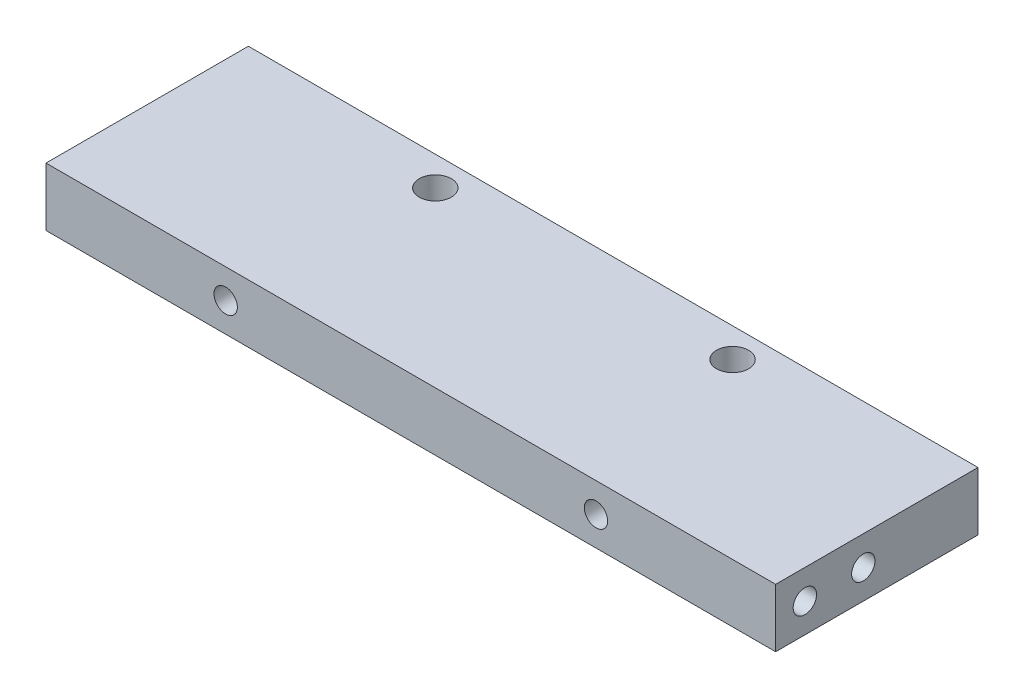
SolidWorks part; units mm, degrees
material "6061-T6 (SS)"
ref_plane "前视基准面" through (0, 0, 0) normal (0, 0, 1) x (1, 0, 0)
ref_plane "上视基准面" through (0, 0, 0) normal (0, 1, 0) x (1, 0, 0)
ref_plane "右视基准面" through (0, 0, 0) normal (1, 0, 0) x (0, 0, -1)
other "Configuration Table"
sketch "草图1" plane through (0, 0, 0) normal (0, 0, 1) x (1, 0, 0)
  line L1 (-0.3, -4.3) -> (49.65, -4.3)
  line L2 (-0.3, -4.3) -> (-0.3, -0.3)
  line L3 (-0.3, -0.3) -> (49.65, -0.3)
  line L4 (49.65, -4.3) -> (49.65, -0.3)
  dimension "D1" = 49.65
  dimension "D2" = 0.3
  dimension "D3" = 0.3
  dimension "D4" = 4.3
extrude "Main_Stock" add sketch "草图1" along normal blind 8.8519 from offset 2.2481
sketch "草图2" plane through (0, 0, 11.1) normal (0, 0, 1) x (1, 0, 0)
  circle A0 centre (12, -2.3) radius 0.8
  circle A1 centre (37.35, -2.3) radius 0.8
  dimension "D1" = 1.6
  dimension "D2" = 12
  dimension "D3" = 37.35
  dimension "D4" = 2.3
extrude "Frame_2xD1p6_Through" cut sketch "草图2" against normal through all
cosmetic thread "Frame_M2_Through_Cosmetic_1" parameters "D2"=2
cosmetic thread "Frame_M2_Through_Cosmetic_2" parameters "D2"=2
sketch "草图3" plane through (-0.3, 0, 0) normal (-1, 0, 0) x (0, 0, 1)
  circle A0 centre (5.1, -2.3) radius 0.8
  circle A1 centre (9.1, -2.3) radius 0.8
  dimension "D1" = 1.6
  dimension "D2" = 5.1
  dimension "D3" = 9.1
  dimension "D4" = 2.3
extrude "Corner_L_2xD1p6_Blind5" cut sketch "草图3" against normal blind 5
cosmetic thread "Corner_L_M2_Cosmetic_1" parameters "D1"=4.5, "D2"=2
cosmetic thread "Corner_L_M2_Cosmetic_2" parameters "D1"=4.5, "D2"=2
sketch "草图4" plane through (49.65, 0, 0) normal (1, 0, 0) x (0, 0, -1)
  circle A0 centre (-5.1, -2.3) radius 0.8
  circle A1 centre (-9.1, -2.3) radius 0.8
  dimension "D1" = 1.6
  dimension "D2" = 5.1
  dimension "D3" = 9.1
  dimension "D4" = 2.3
extrude "Corner_R_2xD1p6_Blind5" cut sketch "草图4" against normal blind 5
cosmetic thread "Corner_R_M2_Cosmetic_1" parameters "D1"=4.5, "D2"=2
cosmetic thread "Corner_R_M2_Cosmetic_2" parameters "D1"=4.5, "D2"=2
sketch "草图5" plane through (0, 0, 2.2481) normal (0, 0, -1) x (-1, 0, 0)
  line L1 (0.3, -4.3) -> (-49.65, -4.3)
  line L2 (0.3, -4.3) -> (0.3, -0.3)
  line L3 (0.3, -0.3) -> (-49.65, -0.3)
  line L4 (-49.65, -4.3) -> (-49.65, -0.3)
  dimension "D1" = 0.3
  dimension "D2" = 49.65
  dimension "D3" = 0.3
  dimension "D4" = 4.3
extrude "Wall_Extension_To_Floor" add sketch "草图5" along normal blind 5
sketch "草图6" plane through (0, -4.3, 0) normal (0, -1, 0) x (1, 0, 0)
  circle A0 centre (14.5, -0.75) radius 1.1
  circle A1 centre (34.85, -0.75) radius 1.1
  dimension "D1" = 2.2
  dimension "D2" = 14.5
  dimension "D3" = 34.85
  dimension "D4" = 0.75
extrude "Horizontal_Base_M2_1_-0.0043" cut sketch "草图6" against normal blind 4.01
